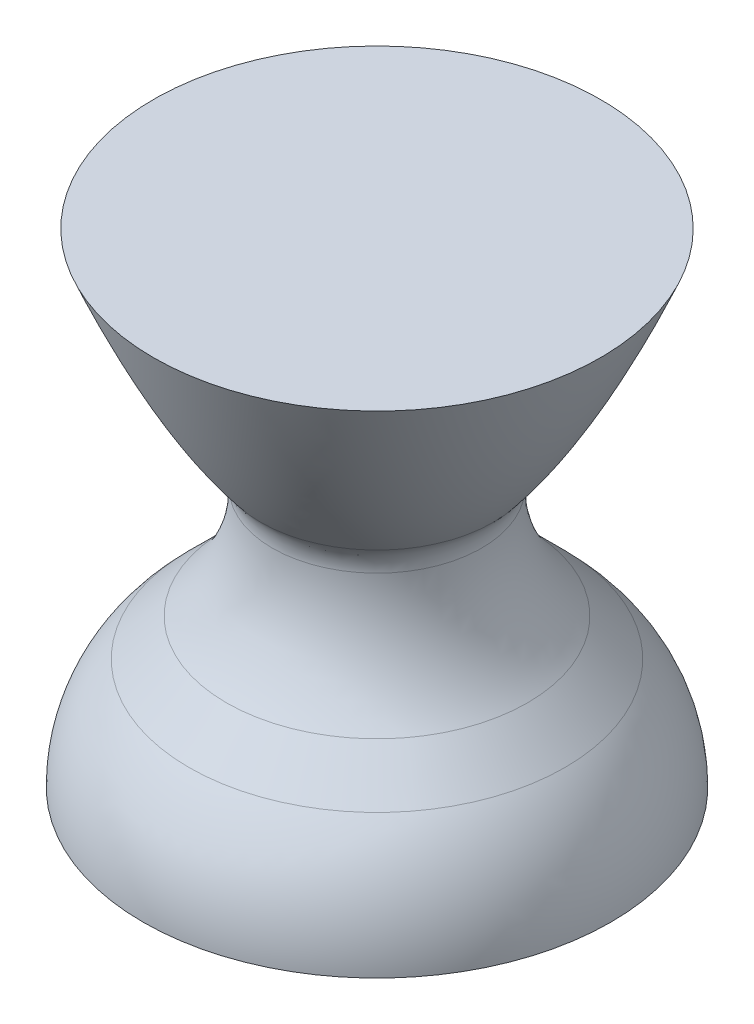
SolidWorks part; units mm, degrees
ref_plane "Front Plane" through (0, 0, 0) normal (0, 0, 1) x (1, 0, 0)
ref_plane "Top Plane" through (0, 0, 0) normal (0, 1, 0) x (1, 0, 0)
ref_plane "Right Plane" through (0, 0, 0) normal (1, 0, 0) x (0, 0, -1)
sketch "Sketch1" plane through (0, 0, 0) normal (1, 0, 0) x (0, 0, -1)
  line L0 (0, 66.7492) -> (0, -102.0008) construction
  line L1 (24.0991, 0) -> (0, 0) construction
  line L3 (51.5099, 51.7202) -> (0, 51.7202)
  line L4 (0, 51.7202) -> (0, -59.7253)
  line L5 (0, -59.7253) -> (53.8871, -59.7253)
  spline S0 degree 2 poles (26.7953, 6.5092) (39.1526, 21.98) (51.5099, 51.7202) knots 0 0 0 1 1 1 construction
  spline S1 degree 2 poles (26.7953, 6.5092) (39.1526, 21.98) (51.5099, 51.7202) knots 0 0 0 1 1 1
  spline S2 degree 4 poles (24.1269, -0.7181) (24.126, -0.702) (24.1243, -0.674) (24.121, -0.6548) (24.115, -0.5168) (24.1058, -0.4371) (24.0994, -0.1068) (24.0979, 0.0016) (24.102, 0.2676) (24.1085, 0.4271) (24.1205, 0.6468) (24.1414, 0.9014) (24.1752, 1.2025) (24.2265, 1.5421) (24.2905, 1.881) (24.3671, 2.2164) (24.4563, 2.5492) (24.5577, 2.8781) (24.6716, 3.2033) (24.7972, 3.5236) (24.9353, 3.8397) (25.0841, 4.1493) (25.246, 4.4548) (25.4165, 4.7513) (25.6025, 5.0457) (25.7918, 5.3255) (26.0044, 5.6107) (26.1789, 5.8329) (26.3663, 6.05) (26.5046, 6.2086) (26.757, 6.4727) (26.837, 6.5524) (27.1016, 6.8058) (27.1881, 6.8781) (27.2854, 6.9666) (27.3038, 6.9802) (27.3264, 7.0002) knots 0 0 0 0 0 0.005192 0.010384 0.020768 0.041536 0.082569 0.102427 0.122284 0.142142 0.162 0.201716 0.241431 0.281147 0.320863 0.360578 0.400294 0.44001 0.479725 0.519441 0.559156 0.598872 0.638588 0.678303 0.718019 0.757735 0.79745 0.837166 0.857024 0.876882 0.916597 0.958047 0.979024 0.989512 1 1 1 1 1 construction
  spline S3 degree 4 poles (24.0991, 0) (24.0991, 0.0359) (24.0996, 0.1101) (24.102, 0.2676) (24.1085, 0.4271) (24.1205, 0.6468) (24.1414, 0.9014) (24.1752, 1.2025) (24.2265, 1.5421) (24.2905, 1.881) (24.3671, 2.2164) (24.4563, 2.5492) (24.5577, 2.8781) (24.6716, 3.2033) (24.7972, 3.5236) (24.9353, 3.8397) (25.0841, 4.1493) (25.246, 4.4548) (25.4165, 4.7513) (25.6025, 5.0457) (25.7918, 5.3255) (26.0044, 5.6107) (26.1789, 5.8329) (26.3663, 6.05) (26.5046, 6.2086) (26.6704, 6.3821) (26.7445, 6.4585) (26.7953, 6.5092) knots 0.082569 0.082569 0.082569 0.082569 0.082569 0.102427 0.122284 0.142142 0.162 0.201716 0.241431 0.281147 0.320863 0.360578 0.400294 0.44001 0.479725 0.519441 0.559156 0.598872 0.638588 0.678303 0.718019 0.757735 0.79745 0.837166 0.857024 0.876882 0.916597 0.916597 0.916597 0.916597 0.916597
  spline S4 degree 4 poles (24.2082, 2.8078) (24.2014, 2.7164) (24.1882, 2.5516) (24.1642, 2.1752) (24.1352, 1.6879) (24.1148, 1.1016) (24.103, 0.6554) (24.0988, 0.1102) (24.0988, -0.1001) (24.102, -0.5432) (24.1083, -0.8242) (24.1178, -1.1948) (24.1304, -1.5134) (24.1462, -1.8619) (24.1652, -2.1937) (24.1928, -2.6181) (24.2323, -3.122) (24.3033, -3.88) (24.4231, -4.8865) (24.5995, -6.0567) (24.8509, -7.3852) (25.1518, -8.7036) (25.5018, -10.0096) (25.9004, -11.3018) (26.3469, -12.5781) (26.841, -13.8369) (27.3817, -15.0762) (27.9685, -16.2946) (28.6001, -17.4899) (29.2765, -18.6613) (29.9954, -19.8057) (30.758, -20.9239) (31.4592, -21.8744) (32.0887, -22.6734) (32.6241, -23.3204) (33.0723, -23.84) (33.5085, -24.3298) (33.9358, -24.7885) (34.2456, -25.1139) (34.6121, -25.486) (34.7661, -25.64) (35.1509, -26.0189) (35.4776, -26.3288) (35.905, -26.7274) (36.2395, -27.0244) (36.5192, -27.2709) (36.6465, -27.38) (36.7148, -27.4388) (36.7496, -27.4687) knots 0 0 0 0 0 0.010393 0.020785 0.041571 0.062104 0.072371 0.082638 0.092575 0.102512 0.112449 0.122387 0.132324 0.142261 0.152198 0.162135 0.18201 0.201884 0.241633 0.281382 0.32113 0.360879 0.400628 0.440377 0.480126 0.519874 0.559623 0.599372 0.639121 0.67887 0.718618 0.758367 0.798116 0.81799 0.837865 0.857739 0.877613 0.897488 0.907425 0.917362 0.927629 0.937896 0.958429 0.979215 0.989607 0.994804 1 1 1 1 1 construction
  spline S5 degree 4 poles (24.0991, 0) (24.0991, -0.0705) (24.0996, -0.2136) (24.102, -0.5432) (24.1083, -0.8242) (24.1178, -1.1948) (24.1304, -1.5134) (24.1462, -1.8619) (24.1652, -2.1937) (24.1928, -2.6181) (24.2323, -3.122) (24.3033, -3.88) (24.4231, -4.8865) (24.5995, -6.0567) (24.8509, -7.3852) (25.1518, -8.7036) (25.5018, -10.0096) (25.9004, -11.3018) (26.3469, -12.5781) (26.841, -13.8369) (27.3817, -15.0762) (27.9685, -16.2946) (28.6001, -17.4899) (29.2765, -18.6613) (29.9954, -19.8057) (30.758, -20.9239) (31.4592, -21.8744) (32.0887, -22.6734) (32.6241, -23.3204) (33.0723, -23.84) (33.5085, -24.3298) (33.9358, -24.7885) (34.2456, -25.1139) (34.5369, -25.4096) (34.6364, -25.5099) (34.6863, -25.5598) knots 0.082638 0.082638 0.082638 0.082638 0.082638 0.092575 0.102512 0.112449 0.122387 0.132324 0.142261 0.152198 0.162135 0.18201 0.201884 0.241633 0.281382 0.32113 0.360879 0.400628 0.440377 0.480126 0.519874 0.559623 0.599372 0.639121 0.67887 0.718618 0.758367 0.798116 0.81799 0.837865 0.857739 0.877613 0.897488 0.907425 0.917362 0.917362 0.917362 0.917362 0.917362
  spline S6 degree 1 poles (34.6863, -25.5598) (43.2939, -34.1675) knots 0 0 1 1 construction
  spline S7 degree 1 poles (34.6863, -25.5598) (43.2939, -34.1675) knots 0 0 1 1
  spline S8 degree 4 poles (53.7786, -62.5331) (53.7854, -62.4443) (53.7986, -62.2715) (53.8165, -61.9995) (53.837, -61.6578) (53.8539, -61.2899) (53.8674, -60.9636) (53.8775, -60.5731) (53.8842, -60.2918) (53.8874, -59.831) (53.8874, -59.6282) (53.8841, -59.1794) (53.8777, -58.9026) (53.8682, -58.5304) (53.8554, -58.2107) (53.8356, -57.7794) (53.8055, -57.2788) (53.7611, -56.6859) (53.6821, -55.8464) (53.582, -55.0061) (53.4611, -54.1704) (53.291, -53.1704) (53.096, -52.1755) (52.8701, -51.1866) (52.6135, -50.2056) (52.3326, -49.2313) (52.0274, -48.2642) (51.6364, -47.1475) (51.1421, -45.8888) (50.601, -44.6495) (50.0141, -43.4314) (49.3819, -42.2359) (48.7056, -41.0651) (47.9857, -39.9201) (47.2241, -38.8034) (46.5207, -37.8509) (45.8942, -37.0553) (45.3533, -36.4031) (44.9155, -35.8941) (44.5151, -35.4469) (44.1817, -35.0846) (43.8741, -34.7604) (43.6742, -34.5516) (43.3653, -34.2384) (43.2159, -34.0891) (42.8276, -33.7069) (42.5039, -33.4001) (42.0738, -32.9991) (41.7409, -32.7038) (41.4603, -32.4565) (41.3334, -32.3478) (41.2649, -32.2889) (41.2301, -32.259) knots 0 0 0 0 0 0.010393 0.020785 0.031178 0.041571 0.051838 0.062104 0.072371 0.082638 0.092575 0.102512 0.112449 0.122387 0.132324 0.142261 0.162135 0.18201 0.201884 0.241633 0.261507 0.281382 0.32113 0.360879 0.380754 0.400628 0.440377 0.480126 0.519874 0.559623 0.599372 0.639121 0.67887 0.718618 0.758367 0.798116 0.81799 0.837865 0.857739 0.877613 0.887551 0.897488 0.907425 0.917362 0.927629 0.937896 0.958429 0.979215 0.989607 0.994804 1 1 1 1 1 construction
  spline S9 degree 4 poles (53.8871, -59.7253) (53.8871, -59.6548) (53.8866, -59.5132) (53.8841, -59.1794) (53.8777, -58.9026) (53.8682, -58.5304) (53.8554, -58.2107) (53.8356, -57.7794) (53.8055, -57.2788) (53.7611, -56.6859) (53.6821, -55.8464) (53.582, -55.0061) (53.4611, -54.1704) (53.291, -53.1704) (53.096, -52.1755) (52.8701, -51.1866) (52.6135, -50.2056) (52.3326, -49.2313) (52.0274, -48.2642) (51.6364, -47.1475) (51.1421, -45.8888) (50.601, -44.6495) (50.0141, -43.4314) (49.3819, -42.2359) (48.7056, -41.0651) (47.9857, -39.9201) (47.2241, -38.8034) (46.5207, -37.8509) (45.8942, -37.0553) (45.3533, -36.4031) (44.9155, -35.8941) (44.5151, -35.4469) (44.1817, -35.0846) (43.8741, -34.7604) (43.6742, -34.5516) (43.4444, -34.3186) (43.3438, -34.2173) (43.2939, -34.1675) knots 0.082638 0.082638 0.082638 0.082638 0.082638 0.092575 0.102512 0.112449 0.122387 0.132324 0.142261 0.162135 0.18201 0.201884 0.241633 0.261507 0.281382 0.32113 0.360879 0.380754 0.400628 0.440377 0.480126 0.519874 0.559623 0.599372 0.639121 0.67887 0.718618 0.758367 0.798116 0.81799 0.837865 0.857739 0.877613 0.887551 0.897488 0.907425 0.917362 0.917362 0.917362 0.917362 0.917362
  dimension "D1" = 24.0991
  dimension "D2" = 51.5099
  dimension "D3" = 53.8871
  dimension "D4" = 34.6863
  dimension "D5" = 43.2939
  dimension "D6" = 26.7953
  dimension "D7" = 25.5598
revolve "Revolve2" add sketch "Sketch1" angle 360 about L0
